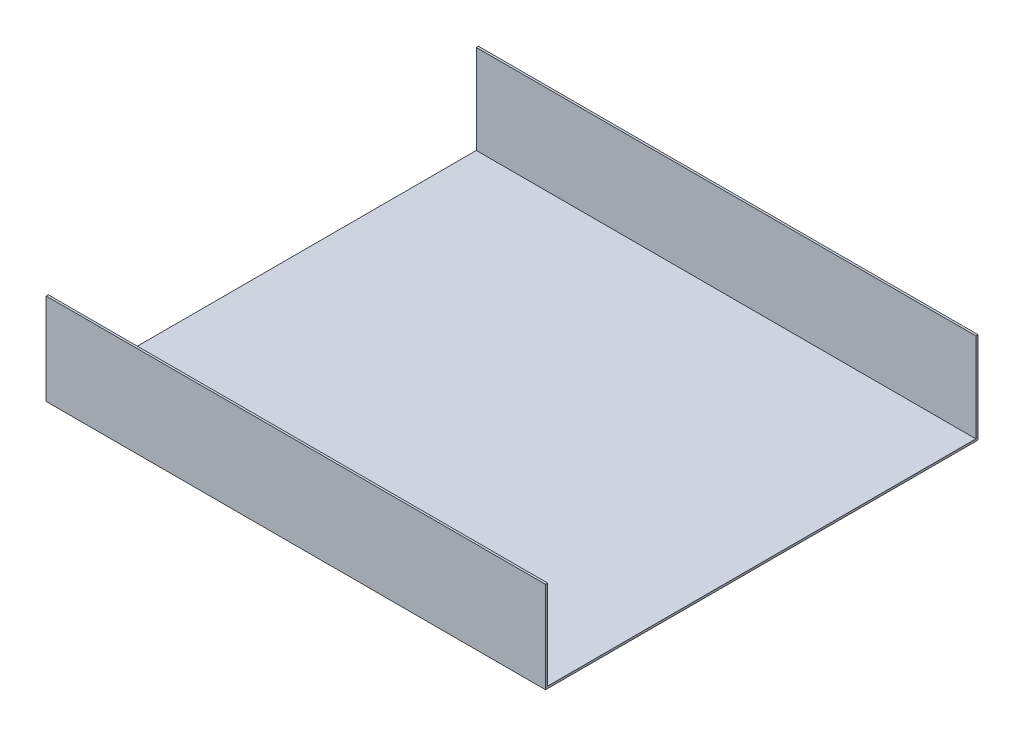
SolidWorks part; units mm, degrees
material "AISI 304"
ref_plane "Alzado" through (0, 0, 0) normal (0, 0, 1) x (1, 0, 0)
ref_plane "Planta" through (0, 0, 0) normal (0, 1, 0) x (1, 0, 0)
ref_plane "Vista lateral" through (0, 0, 0) normal (1, 0, 0) x (0, 0, -1)
sketch "Croquis1" plane through (0, 0, 0) normal (1, 0, 0) x (0, 0, -1)
  line L0 (0, 25) -> (0, 0)
  line L1 (0, 0) -> (120, 0)
  line L2 (120, 0) -> (120, 25)
  line L3 (0, 25) -> (120, 25)
  dimension "D1" = 120
  dimension "D2" = 25
extrude "Saliente-Extruir1" add sketch "Croquis1" along normal blind 140
shell "Vaciado1" thickness 0.6 removed face at (0, 12.5, -60) removed face at (140, 12.5, -60) removed face at (70, 25, -60) outward yes
